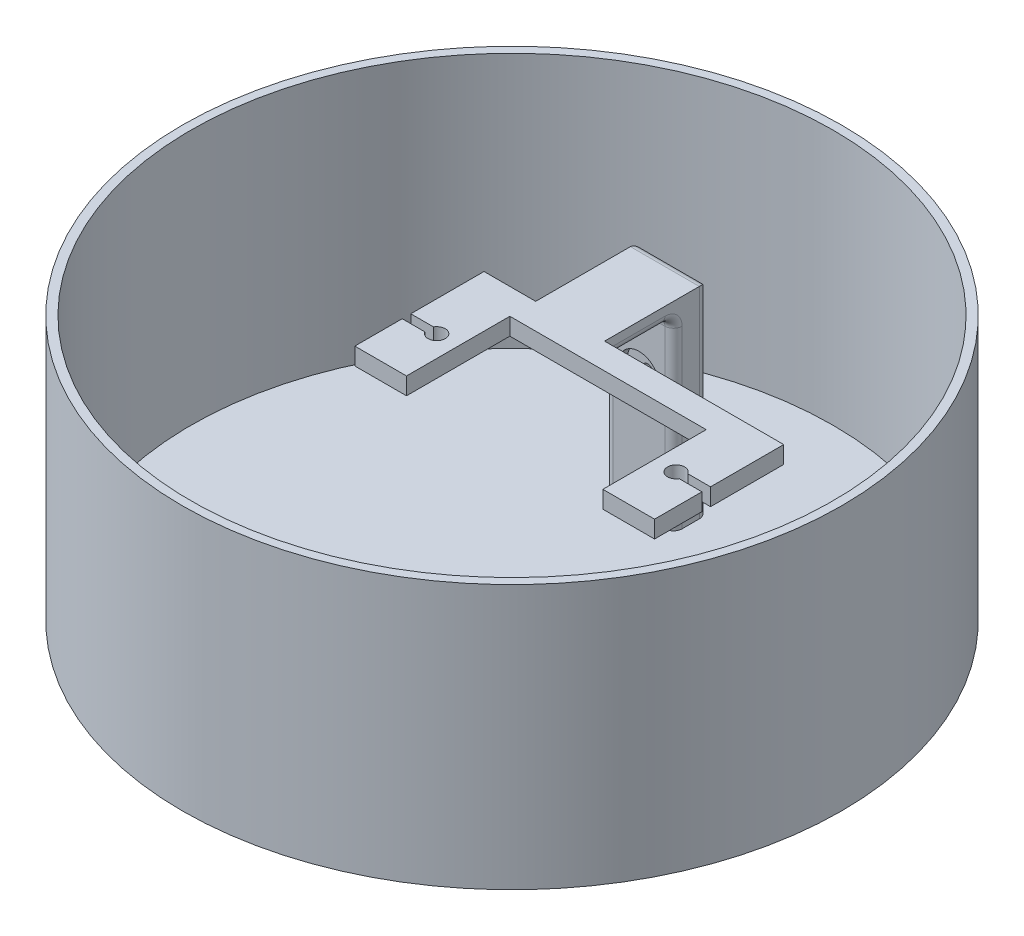
SolidWorks part; units mm, degrees
ref_plane "Front Plane" through (0, 0, 0) normal (0, 0, 1) x (1, 0, 0)
ref_plane "Top Plane" through (0, 0, 0) normal (0, 1, 0) x (1, 0, 0)
ref_plane "Right Plane" through (0, 0, 0) normal (1, 0, 0) x (0, 0, -1)
sketch "Sketch1" plane through (0, 0, 0) normal (0, 1, 0) x (1, 0, 0)
  line L0 (-11.4, -6) -> (-17.4, -6)
  line L2 (-11.4, -6) -> (-11.4, 6)
  line L3 (-11.4, 6) -> (11.4, 6)
  line L4 (11.4, -6) -> (11.4, 6)
  line L5 (-17.4, -6) -> (-17.4, -0.5)
  line L6 (-17.4, 9) -> (-11.4, 9)
  line L7 (17.4, 9) -> (17.4, 0.5)
  line L8 (17.4, -6) -> (11.4, -6)
  line L9 (-3.4, 9) -> (17.4, 9)
  line L11 (-11.4, 9) -> (-11.4, 17)
  line L12 (-11.4, 17) -> (-3.4, 17)
  line L13 (-3.4, 9) -> (-3.4, 17)
  line L14 (-17.4, 0.5) -> (-17.4, 9)
  line L15 (-14.766, 0.5) -> (-17.4, 0.5)
  line L17 (-14.766, -0.5) -> (-17.4, -0.5)
  line L19 (0, 0) -> (0, 3.2348) construction
  line L20 (14.766, -0.5) -> (17.4, -0.5)
  line L21 (14.766, 0.5) -> (17.4, 0.5)
  line L22 (17.4, -0.5) -> (17.4, -6)
  arc A0 (-14.766, -0.5) -> (-14.766, 0.5) centre (-13.9, 0) ccw
  arc A2 (14.766, -0.5) -> (14.766, 0.5) centre (13.9, 0) cw
  point P4 (0, 6)
  point P6 (-11.4, 0)
  point P16 (-7.4, 17)
  dimension "D8" = 2
  dimension "D10" = 1
  dimension "D1" = 22.8
  dimension "D2" = 12
  dimension "D3" = 6
  dimension "D4" = 3
  dimension "D5" = 8
  dimension "D6" = 10
  dimension "D7" = 8
  dimension "D9" = 2.5
  dimension "D11" = 6
extrude "Boss-Extrude1" add sketch "Sketch1" along normal blind 2
sketch "Sketch3" plane through (0, 0, -17) normal (0, 0, -1) x (-1, 0, 0)
  line L1 (3.4, 2) -> (11.4, 2)
  line L2 (3.4, 2) -> (3.4, -11.3749)
  line L3 (3.4, -11.3749) -> (11.4, -11.3749)
  line L4 (11.4, 2) -> (11.4, -11.3749)
extrude "Boss-Extrude2" add sketch "Sketch3" along normal blind 4
sketch3d "3DSketch1"
  line L0 (-11.4, 2, -21) -> (-3.4, 2, -21) construction
  point P2 (-7.4, 2, -21)
fillet "Fillet1" radius 1 8 edges at (-3.4, 0, -13) (-11.4, 0, -13) (-3.4, -5.6874, -17) (-3.4, -4.6874, -21) (-11.4, -4.6874, -21) (-11.4, -5.6874, -17) (-7.4, 2, -21) (-7.4, 0, -17)
sketch "Sketch4" plane through (0, 0, -21) normal (0, 0, -1) x (-1, 0, 0)
  line L0 (4.4, -11.3749) -> (10.4, -11.3749) construction
  circle A0 centre (7.4, -7.3749) radius 2.35
  circle A1 centre (7.4, -7.3749) radius 0.6
  point P2 (7.4, -11.3749)
  dimension "D2" = 4.7
  dimension "D3" = 1.2
  dimension "D1" = 4
extrude "Cut-Extrude1" cut sketch "Sketch4" against normal blind 2 contours A0 A1 | A1 region at (-5.1165, -7.3749, -21) region at (-7.4, -7.3749, -21)
extrude "Cut-Extrude2" cut sketch "Sketch4<4>" against normal up to surface (4 mm away) contours A1 region at (-7.4, -7.3749, -21) up to face at (-7.4, -6.1874, -17)
sketch "Sketch4<4>" plane through (0, 0, -21) normal (0, 0, -1) x (-1, 0, 0) same geometry as "Sketch4"
extrude "Cut-Extrude3" cut sketch "Sketch4<5>" along normal offset from surface (1 mm away) 1 from surface up to face at (-7.4, -6.7749, -19) starting at face at (-8, -7.3749, -17)
sketch "Sketch4<5>" plane through (0, 0, -21) normal (0, 0, -1) x (-1, 0, 0) same geometry as "Sketch4"
sketch "Sketch5" plane through (0, 0, -18) normal (0, 0, 1) x (1, 0, 0)
  circle A0 centre (-7.4, -7.3749) radius 26.7693
  circle A1 centre (-7.4, -7.3749) radius 2.35
sketch "Sketch6" plane through (0, -11.3749, 0) normal (0, -1, 0) x (1, 0, 0)
  circle A0 centre (-5.05, 0.1) radius 37.2808
extrude "Boss-Extrude3" add sketch "Sketch6" along normal blind 1 from offset 10 separate body
extrude "Extrude-Thin1" add sketch "Sketch6<2>" against normal offset from surface (30.6849 mm away) 1 from surface thin up to face at (-9.75, -7.3749, -21) starting at face at (-5.05, -22.3749, -37.1808) thin type one direction wall 1
sketch "Sketch6<2>" plane through (0, -11.3749, 0) normal (0, -1, 0) x (1, 0, 0) same geometry as "Sketch6"
sketch "Sketch7" plane through (0, -11.3749, 0) normal (0, -1, 0) x (1, 0, 0)
  line L4 (-3.4, -20) -> (-3.4, -18)
  line L5 (-4.4, -17) -> (-10.4, -17)
  line L6 (-11.4, -18) -> (-11.4, -20)
  line L7 (-10.4, -21) -> (-4.4, -21)
  line L8 (-3.4, -20) -> (-3.4, -18)
  line L9 (-4.4, -17) -> (-10.4, -17)
  line L10 (-11.4, -18) -> (-11.4, -20)
  line L11 (-10.4, -21) -> (-4.4, -21)
  arc A4 (-3.4, -18) -> (-4.4, -17) centre (-4.4, -18) ccw
  arc A5 (-10.4, -17) -> (-11.4, -18) centre (-10.4, -18) ccw
  arc A6 (-11.4, -20) -> (-10.4, -21) centre (-10.4, -20) ccw
  arc A7 (-4.4, -21) -> (-3.4, -20) centre (-4.4, -20) ccw
  arc A8 (-3.4, -18) -> (-4.4, -17) centre (-4.4, -18) ccw
  arc A9 (-10.4, -17) -> (-11.4, -18) centre (-10.4, -18) ccw
  arc A10 (-11.4, -20) -> (-10.4, -21) centre (-10.4, -20) ccw
  arc A11 (-4.4, -21) -> (-3.4, -20) centre (-4.4, -20) ccw
  dimension "D1" = 0
extrude "Boss-Extrude4" add sketch "Sketch7" along normal up to surface (10 mm away) up to face at (-5.05, -21.3749, -37.1808)
